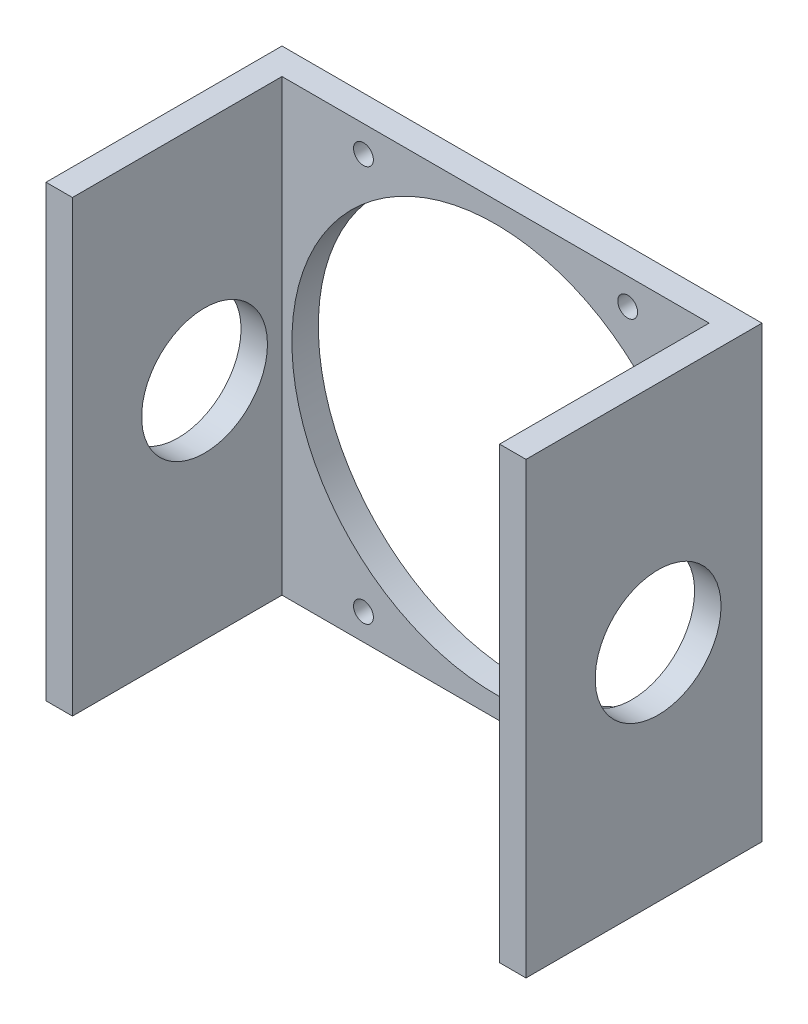
SolidWorks part; units mm, degrees
ref_plane "Front Plane" through (0, 0, 0) normal (0, 0, 1) x (1, 0, 0)
ref_plane "Top Plane" through (0, 0, 0) normal (0, 1, 0) x (1, 0, 0)
ref_plane "Right Plane" through (0, 0, 0) normal (1, 0, 0) x (0, 0, -1)
sketch "Sketch1" plane through (0, 0, 0) normal (0, 1, 0) x (1, 0, 0)
  line L0 (-47.5, -29.9135) -> (47.5, -29.9135) construction
  line L1 (-47.5, 56.6115) -> (47.5, 56.6115) construction
  line L2 (-47.5, 56.6115) -> (-47.5, -56.6115) construction
  line L3 (-47.5, -56.6115) -> (47.5, -56.6115) construction
  line L4 (47.5, 56.6115) -> (47.5, -56.6115) construction
  line L5 (-47.5, 56.6115) -> (47.5, -56.6115) construction
  line L6 (-47.5, -56.6115) -> (47.5, 56.6115) construction
  line L7 (-47.5, -23.9135) -> (47.5, -23.9135) construction
  line L8 (-47.5, 23.5865) -> (47.5, 23.5865) construction
  line L9 (47.5, 27.5865) -> (-47.5, 27.5865) construction
  line L10 (97.198, 47.5) -> (97.198, -47.5) construction
  line L11 (183.723, 47.5) -> (183.723, -47.5) construction
  line L12 (183.723, 47.5) -> (70.5, 47.5) construction
  line L13 (70.5, 47.5) -> (70.5, -47.5) construction
  line L14 (183.723, -47.5) -> (70.5, -47.5) construction
  line L15 (183.723, 47.5) -> (70.5, -47.5) construction
  line L16 (70.5, 47.5) -> (183.723, -47.5) construction
  line L17 (103.198, 47.5) -> (103.198, -47.5) construction
  line L18 (150.698, 47.5) -> (150.698, -47.5) construction
  line L19 (154.698, -47.5) -> (154.698, 47.5) construction
  line L20 (64.5, 88.7731) -> (64.5, -54.5) construction
  line L21 (47.5, -56.6115) -> (-248.4804, -56.6115) construction
  line L22 (47.5, -56.6115) -> (47.5, -62.6115) construction
  line L23 (47.5, -62.6115) -> (-248.4804, -62.6115) construction
  line L24 (-248.4804, -56.6115) -> (-248.4804, -62.6115) construction
  line L25 (64.5, -54.5) -> (327.1082, -54.5) construction
  line L26 (70.5, 94.7731) -> (70.5, -48.5) construction
  line L27 (70.5, -48.5) -> (327.1082, -48.5) construction
  line L28 (70.5, -48.5) -> (70.5, -54.5) construction
  line L29 (70.5, -48.5) -> (64.5, -48.5) construction
  line L30 (47.5, -56.6115) -> (47.5, -62.6115) construction
  line L31 (48.5, 17.5865) -> (48.5, -30) construction
  line L32 (48.5, -30) -> (54.5, -30) construction
  line L33 (54.5, -30) -> (54.5, 23.5865) construction
  line L34 (0, 0) -> (0, 56.6115) construction
  line L35 (-48.5, -30) -> (-54.5, -30) construction
  line L36 (-54.5, -30) -> (-54.5, 23.5865) construction
  line L37 (-48.5, 17.5865) -> (-48.5, -30) construction
  line L38 (54.5, 23.5865) -> (-54.5, 23.5865) construction
  line L39 (-48.5, 17.5865) -> (48.5, 17.5865) construction
  line L40 (48.5, 17.5865) -> (48.5, 23.5865) construction
  line L41 (70.5, 94.7731) -> (-59.952, 94.7731) construction
  line L42 (64.5, 88.7731) -> (-64.5, 88.7731) construction
  line L43 (-64.5, 88.7731) -> (-64.5, -48.5) construction
  line L44 (-64.5, -48.5) -> (-70.5, -48.5) construction
  line L45 (-70.5, -48.5) -> (-70.5, 98.5172) construction
  line L46 (-196.6321, -56.6115) -> (-196.6321, 23.9185) construction
  line L51 (-196.6321, -62.6115) -> (-101.6321, -62.6115) construction
  line L52 (-196.6321, -62.6115) -> (-196.6321, -89.3115) construction
  line L53 (-196.6321, -89.3115) -> (-101.6321, -89.3115) construction
  line L54 (-101.6321, -62.6115) -> (-101.6321, -89.3115) construction
  line L55 (-196.6321, 23.9185) -> (-101.6321, 23.9185) construction
  line L56 (-101.6321, 23.9185) -> (-101.6321, -56.6115) construction
  line L57 (-54.5, -23.9135) -> (-64.5, -23.9135) construction
  line L58 (54.5, -23.9135) -> (64.5, -23.9135) construction
  line L59 (64.5, 88.7731) -> (64.5, 94.7731) construction
  point P0 (0, 0)
  point P17 (127.1115, 0)
  dimension "D1" = 113.223
  dimension "D2" = 95
  dimension "D3" = 6
  dimension "D4" = 26.698
  dimension "D5" = 4
  dimension "D6" = 57.5
  dimension "D7" = 29.025
  dimension "D8" = 6
  dimension "D9" = 95
  dimension "D10" = 6
  dimension "D11" = 26.698
  dimension "D12" = 4
  dimension "D13" = 29.025
  dimension "D14" = 57.5
  dimension "D15" = 30
  dimension "D16" = 1
  dimension "D17" = 1
  dimension "D18" = 10
  dimension "D19" = 26.7
  dimension "D20" = 80.53
sketch "Sketch2" plane through (0, 0, 0) normal (0, 0, 1) x (1, 0, 0)
  line L0 (-47.5, 0) -> (47.5, 0) construction
  line L1 (-47.5, -50) -> (47.5, -50) construction
  line L2 (-47.5, -50) -> (-47.5, 50) construction
  line L3 (-47.5, 50) -> (47.5, 50) construction
  line L4 (47.5, -50) -> (47.5, 50) construction
  line L5 (-47.5, -50) -> (47.5, 50) construction
  line L6 (-47.5, 50) -> (47.5, -50) construction
  line L11 (0, 0) -> (0, 22.5) construction
  line L12 (-196.6321, 0) -> (-101.6321, 0) construction
  line L13 (-196.6321, 0) -> (-101.6321, 0) construction
  line L14 (0, 27.5) -> (-229.1321, 27.5)
  line L15 (-229.1321, 27.5) -> (-229.1321, -27.5)
  line L16 (-229.1321, -27.5) -> (0, -27.5)
  circle A0 centre (0, 0) radius 22.5 construction
  circle A1 centre (0, 22.5) radius 1.5635
  circle A2 centre (22.5, 0) radius 1.5635
  circle A3 centre (0, -22.5) radius 1.5635
  circle A4 centre (-22.5, 0) radius 1.5635
  circle A5 centre (-171.6321, 0) radius 1.5635
  circle A6 centre (-149.1321, 0) radius 22.5 construction
  circle A7 centre (-149.1321, 22.5) radius 1.5635
  circle A8 centre (-126.6321, 0) radius 1.5635
  circle A9 centre (-149.1321, -22.5) radius 1.5635
  arc A10 (0, 27.5) -> (0, -27.5) centre (0, 0) cw
  point P0 (0, 0)
  point P15 (0, 0)
  point P18 (0, 0)
  point P21 (0, 0)
  point P24 (0, 0)
  point P39 (-47.5, 51)
  point P40 (-47.5, -51)
  dimension "D3" = 45
  dimension "D4" = 3.127
  dimension "D7" = 5
  dimension "D1" = 100
  dimension "D2" = 95
  dimension "D8" = 80
  dimension "D9" = 1
  dimension "D6" = 2
  dimension "D5" = 4
extrude "Boss-Extrude1" [suppressed] add sketch "Sketch2" along normal up to vertex from vertex
sketch "Sketch3" plane through (0, 0, 0) normal (0, 1, 0) x (1, 0, 0)
  line L0 (-48.5, -30) -> (-54.5, -30) construction
  line L1 (-48.5, 17.5865) -> (-48.5, -30) construction
  line L2 (-54.5, -30) -> (-54.5, 23.5865) construction
  line L3 (-48.5, 17.5865) -> (48.5, 17.5865) construction
  line L4 (54.5, 23.5865) -> (-54.5, 23.5865) construction
  line L5 (54.5, -30) -> (54.5, 23.5865) construction
  line L6 (48.5, 17.5865) -> (48.5, -30) construction
  line L7 (48.5, -30) -> (54.5, -30) construction
  line L8 (-48.5, -30) -> (-54.5, -30)
  line L9 (-48.5, 17.5865) -> (-48.5, -30)
  line L10 (-54.5, -30) -> (-54.5, 23.5865)
  line L11 (-48.5, 17.5865) -> (48.5, 17.5865)
  line L12 (54.5, 23.5865) -> (-54.5, 23.5865)
  line L13 (54.5, -30) -> (54.5, 23.5865)
  line L14 (48.5, 17.5865) -> (48.5, -30)
  line L15 (48.5, -30) -> (54.5, -30)
extrude "Boss-Extrude2" add sketch "Sketch3" along normal up to vertex (51 mm away) and the other way up to vertex (51 mm away) up to point (-47.5, 51, 0) other way up to point (-47.5, -51, 0)
sketch "Sketch4" plane through (0, 0, -17.5865) normal (0, 0, 1) x (1, 0, 0)
  line L1 (30, -45) -> (-30, -45) construction
  line L2 (30, -45) -> (30, 45) construction
  line L3 (30, 45) -> (-30, 45) construction
  line L4 (-30, -45) -> (-30, 45) construction
  line L5 (30, -45) -> (-30, 45) construction
  line L6 (30, 45) -> (-30, -45) construction
  circle A0 centre (0, 0) radius 46.25
  circle A1 centre (-30, 45) radius 2.25
  circle A2 centre (30, 45) radius 2.25
  circle A3 centre (30, -45) radius 2.25
  circle A4 centre (-30, -45) radius 2.25
  dimension "D1" = 92.5
  dimension "D4" = 4.5
  dimension "D2" = 90
  dimension "D3" = 60
extrude "Cut-Extrude1" cut sketch "Sketch4" against normal through all
sketch "Sketch5" plane through (54.5, 0, 0) normal (1, 0, 0) x (0, 0, -1)
  circle A0 centre (0, 0) radius 14.2875
  point P0 (0, 0)
  dimension "D1" = 28.575
extrude "Cut-Extrude2" cut sketch "Sketch5" against normal through all
